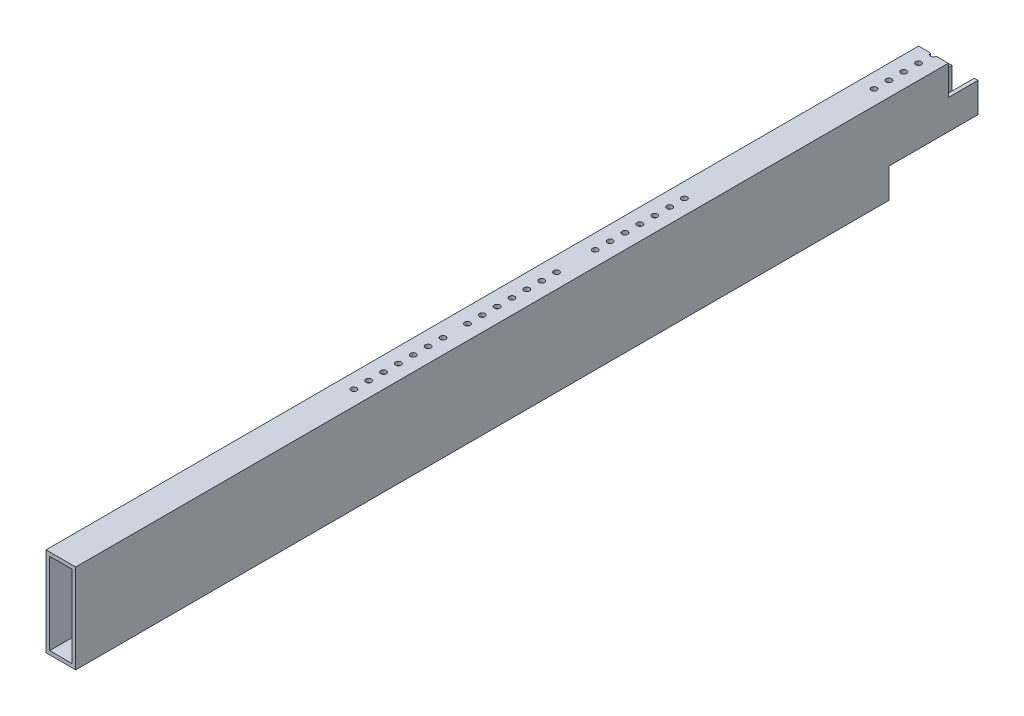
SolidWorks part; units mm, degrees
ref_plane "Front Plane" through (0, 0, 0) normal (0, 0, 1) x (1, 0, 0)
ref_plane "Top Plane" through (0, 0, 0) normal (0, 1, 0) x (1, 0, 0)
ref_plane "Right Plane" through (0, 0, 0) normal (1, 0, 0) x (0, 0, -1)
sketch "Sketch1" plane through (0, 0, 0) normal (0, 0, 1) x (1, 0, 0)
  line L1 (-12.7, -38.1) -> (12.7, -38.1)
  line L2 (-12.7, -38.1) -> (-12.7, 38.1)
  line L3 (-12.7, 38.1) -> (12.7, 38.1)
  line L4 (12.7, -38.1) -> (12.7, 38.1)
  line L5 (-12.7, -38.1) -> (12.7, 38.1) construction
  line L6 (-12.7, 38.1) -> (12.7, -38.1) construction
  point P0 (0, 0)
  dimension "D1" = 25.4
  dimension "D2" = 76.2
extrude "Boss-Extrude1" add sketch "Sketch1" along normal mid plane 771.398
shell "Shell1" thickness 3.175 removed face at (0, 0, -385.699) removed face at (0, 0, 385.699)
sketch "Sketch2" plane through (12.7, 0, 0) normal (1, 0, 0) x (0, 0, -1)
  line L1 (385.699, -38.1) -> (309.499, -38.1)
  line L2 (385.699, -38.1) -> (385.699, -12.7)
  line L3 (385.699, -12.7) -> (309.499, -12.7)
  line L4 (309.499, -38.1) -> (309.499, -12.7)
  dimension "D1" = 25.4
  dimension "D2" = 76.2
extrude "Cut-Extrude1" cut sketch "Sketch2" against normal through all
sketch "Sketch3" plane through (12.7, 0, 0) normal (1, 0, 0) x (0, 0, -1)
  line L1 (385.699, 38.1) -> (360.299, 38.1)
  line L2 (385.699, 38.1) -> (385.699, 12.7)
  line L3 (385.699, 12.7) -> (360.299, 12.7)
  line L4 (360.299, 38.1) -> (360.299, 12.7)
  dimension "D1" = 25.4
extrude "Cut-Extrude2" cut sketch "Sketch3" against normal through all
sketch "Sketch4" plane through (0, 38.1, 0) normal (0, 1, 0) x (1, 0, 0)
  line L0 (-12.7, 360.299) -> (12.7, 360.299) construction
  circle A0 centre (0, 147.3945) radius 2.3812
  circle A1 centre (0, 134.6945) radius 2.3812
  circle A2 centre (0, 121.9945) radius 2.3812
  circle A3 centre (0, 109.2945) radius 2.3812
  circle A4 centre (0, 96.5945) radius 2.3812
  circle A5 centre (0, 83.8945) radius 2.3812
  circle A6 centre (0, 71.1945) radius 2.3812
  circle A7 centre (0, 38.0987) radius 2.3812
  circle A8 centre (0, 25.3987) radius 2.3813
  circle A9 centre (0, 12.6987) radius 2.3813
  circle A10 centre (0, -0.0013) radius 2.3813
  circle A11 centre (0, -12.7013) radius 2.3812
  circle A12 centre (0, -25.4013) radius 2.3812
  circle A13 centre (0, -38.1013) radius 2.3812
  circle A15 centre (0, -58.9932) radius 2.3812
  circle A16 centre (0, -71.6932) radius 2.3812
  circle A17 centre (0, -84.3932) radius 2.3812
  circle A18 centre (0, -97.0932) radius 2.3812
  circle A19 centre (0, -109.7932) radius 2.3812
  circle A20 centre (0, -122.4932) radius 2.3812
  circle A21 centre (0, -135.1932) radius 2.3813
  point P33 (0, 360.299)
  dimension "D1" = 4.7625
  dimension "D3" = 12.7
  dimension "D4" = 12.7
  dimension "D5" = 12.7
  dimension "D6" = 12.7
  dimension "D7" = 12.7
  dimension "D8" = 12.7
  dimension "D9" = 322.2003
  dimension "D10" = 12.7
  dimension "D11" = 12.7
  dimension "D12" = 12.7
  dimension "D13" = 12.7
  dimension "D14" = 12.7
  dimension "D15" = 12.7
  dimension "D16" = 12.7
  dimension "D17" = 419.2922
  dimension "D18" = 12.7
  dimension "D19" = 12.7
  dimension "D20" = 12.7
  dimension "D21" = 12.7
  dimension "D22" = 12.7
  dimension "D2" = 212.9045
extrude "Cut-Extrude3" cut sketch "Sketch4" against normal up to next
sketch "Sketch5" plane through (0, 38.1, 0) normal (0, 1, 0) x (1, 0, 0)
  line L0 (-12.7, 360.299) -> (12.7, 360.299) construction
  circle A0 centre (0, 360.299) radius 2.3813
  circle A1 centre (0, 347.599) radius 2.3813
  circle A2 centre (0, 334.899) radius 2.3813
  circle A3 centre (0, 322.199) radius 2.3813
  circle A4 centre (0, 309.499) radius 2.3813
  dimension "D1" = 4.7625
  dimension "D3" = 12.7
  dimension "D4" = 12.7
  dimension "D5" = 12.7
  dimension "D8" = 0
  dimension "D2" = 12.7
extrude "Cut-Extrude4" cut sketch "Sketch5" against normal up to next
